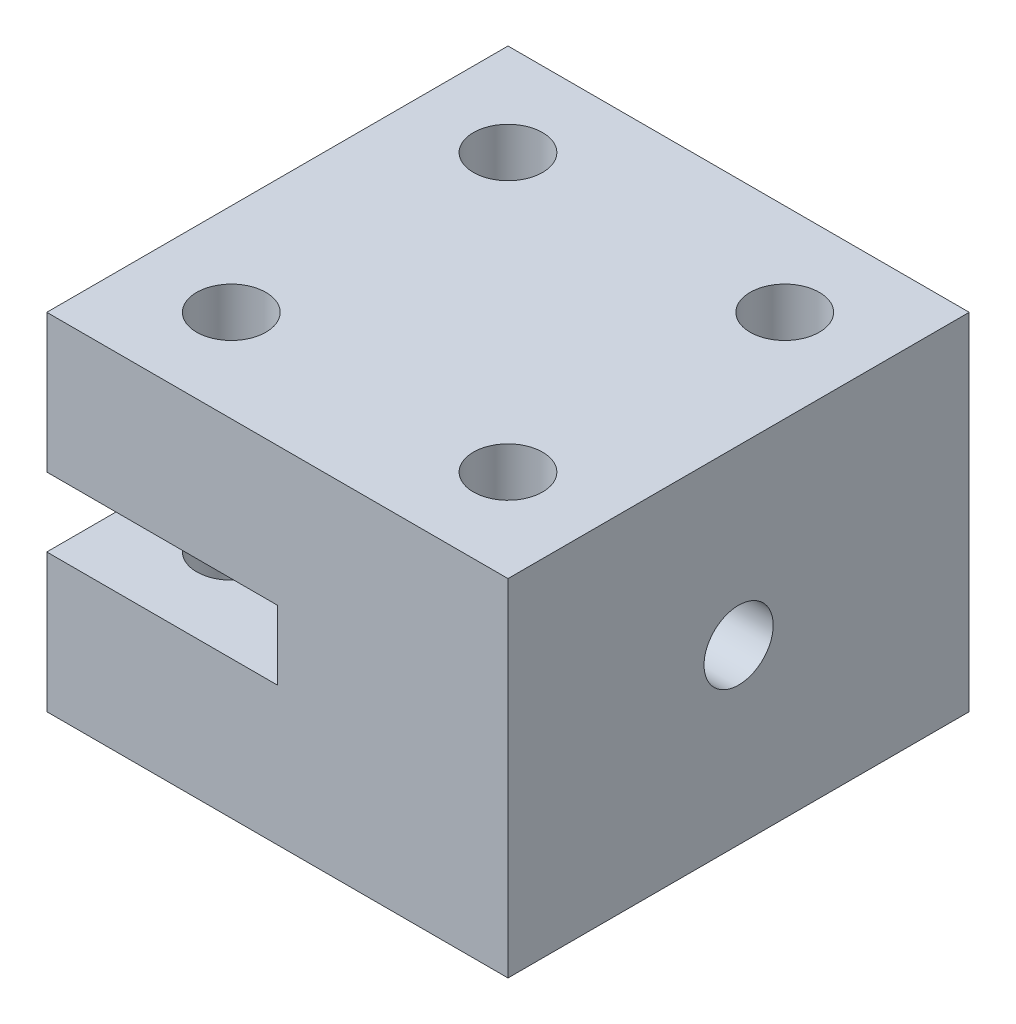
SolidWorks part; units mm, degrees
ref_plane "Front Plane" through (0, 0, 0) normal (0, 0, 1) x (1, 0, 0)
ref_plane "Top Plane" through (0, 0, 0) normal (0, 1, 0) x (1, 0, 0)
ref_plane "Right Plane" through (0, 0, 0) normal (1, 0, 0) x (0, 0, -1)
sketch "Sketch1" plane through (0, 0, 0) normal (0, 1, 0) x (1, 0, 0)
  line L5 (-10, 10) -> (10, 10)
  line L6 (-10, 10) -> (-10, -10)
  line L7 (-10, -10) -> (10, -10)
  line L8 (10, 10) -> (10, -10)
  line L9 (-10, 10) -> (10, -10) construction
  line L10 (-10, -10) -> (10, 10) construction
  point P1 (0, 0)
  dimension "D1" = 20
  dimension "D2" = 20
extrude "Boss-Extrude1" add sketch "Sketch1" along normal mid plane 15
extrude "Cut-Extrude2" cut sketch "Sketch1<3>" against normal mid plane 3
sketch "Sketch1<3>" plane through (0, 0, 0) normal (0, 1, 0) x (1, 0, 0) same geometry as "Sketch1"
sketch "Sketch3" plane through (0, 0, 0) normal (0, 1, 0) x (1, 0, 0)
  line L0 (10, 10) -> (-10, 10) construction
  line L1 (0, 10) -> (10, 10)
  line L2 (0, 10) -> (0, -10)
  line L3 (0, -10) -> (10, -10)
  line L4 (10, 10) -> (10, -10)
extrude "Boss-Extrude2" add sketch "Sketch3" along normal mid plane 3
sketch "Sketch4" plane through (10, 0, 0) normal (1, 0, 0) x (0, 0, -1)
  circle A0 centre (0, 0) radius 1.5
  dimension "D1" = 3
extrude "Cut-Extrude3" cut sketch "Sketch4" against normal blind 7.5
sketch "Sketch5" plane through (0, 0, 0) normal (0, 1, 0) x (1, 0, 0)
  line L1 (-6, 6) -> (6, 6) construction
  line L2 (-6, 6) -> (-6, -6) construction
  line L3 (-6, -6) -> (6, -6) construction
  line L4 (6, 6) -> (6, -6) construction
  line L5 (-6, 6) -> (6, -6) construction
  line L6 (-6, -6) -> (6, 6) construction
  circle A0 centre (-6, 6) radius 1.5
  circle A1 centre (6, 6) radius 1.5
  circle A2 centre (6, -6) radius 1.5
  circle A3 centre (-6, -6) radius 1.5
  point P0 (0, 0)
  point P4 (-6, -6)
  point P9 (0, 0)
  point P11 (5.6323, -6)
  point P13 (-5.6752, -6)
  dimension "D3" = 3
  dimension "D1" = 12
  dimension "D2" = 12
extrude "Cut-Extrude4" cut sketch "Sketch5" against normal through all both and the other way through all
fillet "Fillet1" [suppressed] radius 1
